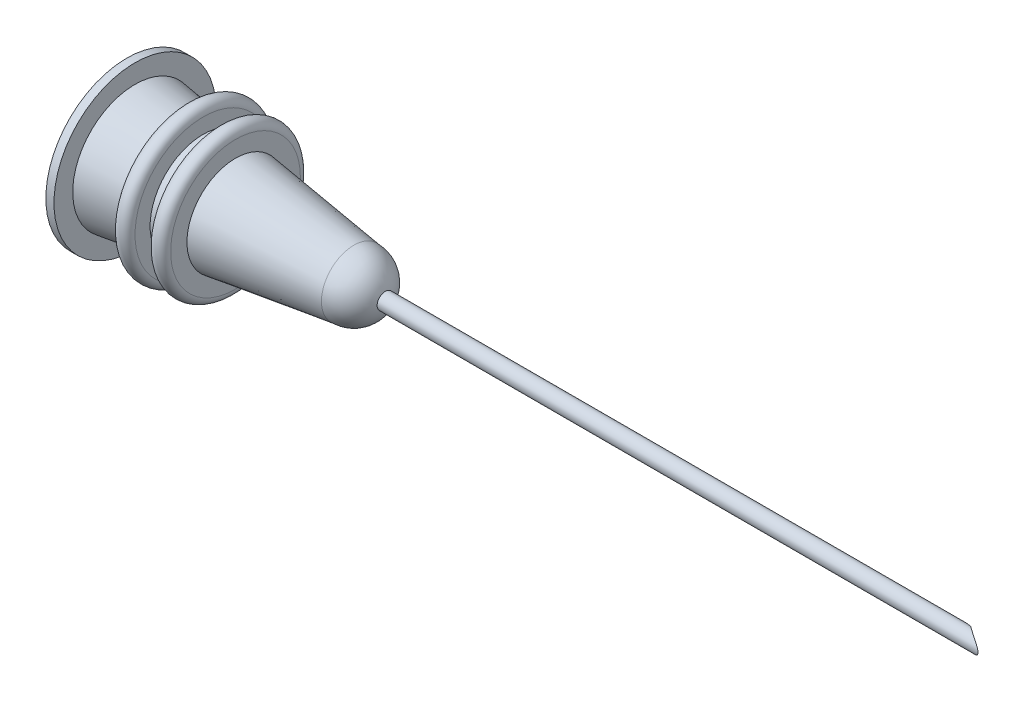
SolidWorks part; units mm, degrees
ref_plane "Front Plane" through (0, 0, 0) normal (0, 0, 1) x (1, 0, 0)
ref_plane "Top Plane" through (0, 0, 0) normal (0, 1, 0) x (1, 0, 0)
ref_plane "Right Plane" through (0, 0, 0) normal (1, 0, 0) x (0, 0, -1)
sketch "Sketch1" plane through (0, 0, 0) normal (0, 0, 1) x (1, 0, 0)
  line L0 (0, 0) -> (-9.4655, 0) construction
  line L1 (0, 0) -> (0, 2)
  line L2 (0, 2) -> (-7.3, 2.9963)
  line L3 (-13.5, 3.8424) -> (-13.5, 5)
  line L4 (-13.5, 5) -> (-14, 5)
  line L5 (-14, 5) -> (-14, 3.1537)
  line L6 (-14, 3.1537) -> (-1, 1.3795)
  line L7 (-1, 1.3795) -> (-1, 0)
  line L8 (-1, 0) -> (0, 0)
  line L9 (-7.3, 4) -> (-7.3, 2.9963)
  line L10 (-8.3, 4) -> (-8.3, 3.1328)
  line L11 (-9.3, 4.2) -> (-9.3, 3.2692)
  line L12 (-10.3, 4.2) -> (-10.3, 3.4057)
  line L13 (-10.3, 3.4057) -> (-13.5, 3.8424)
  line L14 (-8.3, 3.1328) -> (-9.3, 3.2692)
  arc A0 (-7.3, 4) -> (-8.3, 4) centre (-7.8, 4) ccw
  arc A1 (-9.3, 4.2) -> (-10.3, 4.2) centre (-9.8, 4.2) ccw
  dimension "D10" = 1
  dimension "D11" = 1
  dimension "D1" = 1
  dimension "D2" = 5
  dimension "D3" = 0.75
  dimension "D4" = 0.5
  dimension "D5" = 2
  dimension "D6" = 14
  dimension "D7" = 4
  dimension "D8" = 4.2
  dimension "D9" = 2
  dimension "D12" = 7.8
revolve "Revolve1" add sketch "Sketch1" angle 360 about L0
dome "Dome1" faces to dome 1 distance 2 reverse direction no elliptical dome no face at (0, 0, -2) parameters "D1"=2
sketch "Sketch2" plane through (-1, 0, 0) normal (-1, 0, 0) x (0, 0, 1)
  circle A0 centre (0, 0) radius 0.5
  dimension "D1" = 1
extrude "Cut-Extrude1" cut sketch "Sketch2" against normal through all
sketch "Sketch3" plane through (-1, 0, 0) normal (-1, 0, 0) x (0, 0, 1)
  circle A0 centre (0, 0) radius 0.5 construction
  circle A1 centre (0, 0) radius 0.5
extrude "Extrude-Thin1" add sketch "Sketch3" against normal blind 40 thin thin type one direction reverse wall 0.125
sketch "Sketch4" plane through (0, 0, 0) normal (0, 1, 0) x (1, 0, 0)
  line L0 (39, 0) -> (39, 3.5) construction
  line L1 (39, -0.5) -> (39, 0.5) construction
  circle A0 centre (39, 3.5) radius 3.5
  dimension "D1" = 7
extrude "Cut-Extrude2" cut sketch "Sketch4" against normal through all both and the other way through all
sketch "Sketch5" plane through (0, 0, 0) normal (0, 1, 0) x (1, 0, 0)
  line L0 (39, -0.25) -> (39, 7.7622) construction
  line L2 (39, -0.5) -> (41, -0.5) construction
  line L3 (41, -0.5) -> (41, 4.0826) construction
  circle A0 centre (41, 4.0826) radius 5
  dimension "D2" = 10
  dimension "D1" = 2
extrude "Cut-Extrude4" cut sketch "Sketch5" against normal through all both and the other way through all contours A0
